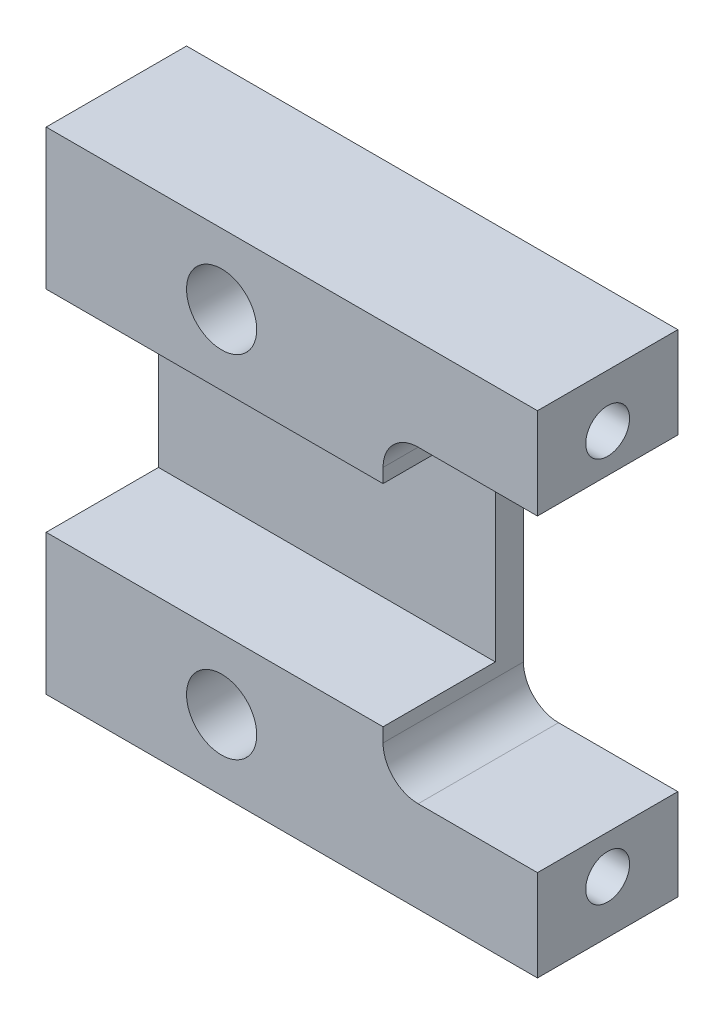
SolidWorks part; units mm, degrees
material "6061-T6 (SS)"
ref_plane "Front Plane" through (0, 0, 0) normal (0, 0, 1) x (1, 0, 0)
ref_plane "Top Plane" through (0, 0, 0) normal (0, 1, 0) x (1, 0, 0)
ref_plane "Right Plane" through (0, 0, 0) normal (1, 0, 0) x (0, 0, -1)
sketch "Sketch1" plane through (0, 0, 0) normal (0, 0, 1) x (1, 0, 0)
  line L1 (-44.45, -44.45) -> (44.45, -44.45)
  line L2 (-44.45, -44.45) -> (-44.45, 44.45)
  line L3 (-44.45, 44.45) -> (44.45, 44.45)
  line L4 (44.45, -44.45) -> (44.45, 44.45)
  line L5 (-44.45, -44.45) -> (44.45, 44.45) construction
  line L6 (-44.45, 44.45) -> (44.45, -44.45) construction
  point P0 (0, 0)
  dimension "D1" = 88.9
  dimension "D2" = 88.9
extrude "Extrude1" add sketch "Sketch1" along normal blind 25.4
sketch "Sketch2" plane through (44.45, 0, 0) normal (1, 0, 0) x (0, 0, -1)
  line L0 (-12.7, 44.45) -> (-12.7, 34.925) construction
  line L1 (-25.4, 44.45) -> (0, 44.45) construction
  dimension "D1" = 9.525
hole_wizard "Tap Drill for 3/8-16 Tap2" positions "Sketch4" profile "Sketch3" hole size "3/8-16" standard "Ansi Inch"
sketch "Sketch4" plane through (44.45, 0, 0) normal (1, 0, 0) x (0, 0, -1)
  point P1 (-12.7, 34.925)
sketch "Sketch3" plane through (44.45, 34.925, 12.7) normal (0, 1, 0) x (0, 0, -1)
  line L0 (0, 0) -> (0, 20.1647)
  line L1 (0, 20.1647) -> (3.9687, 17.78)
  line L2 (3.9687, 17.78) -> (3.9687, 0)
  line L5 (3.9687, 0) -> (0, 0)
  line L10 (0, 20.1647) -> (-3.9688, 17.78) construction
  line L11 (0, -6.35) -> (0, 107.95) construction
  dimension "Hole Dia." = 7.9375
  dimension "Hole Depth" = 17.78
  dimension "Drill Angle" = 118
mirror "Mirror1" about plane through (0, 0, 0) normal (0, 1, 0) of "Tap Drill for 3/8-16 Tap2"
sketch "Sketch5" plane through (0, 0, 25.4) normal (0, 0, 1) x (1, 0, 0)
  line L0 (-12.7, 44.45) -> (-12.7, 31.75) construction
  line L5 (44.45, 44.45) -> (-44.45, 44.45) construction
  line L6 (-44.45, 44.45) -> (-44.45, -44.45) construction
  dimension "D1" = 12.7
  dimension "D2" = 31.75
hole_wizard "1/2 (0.5) Diameter Hole1" positions "Sketch7" profile "Sketch6" hole size "1/2" standard "Ansi Inch" end condition through all
sketch "Sketch7" plane through (0, 0, 25.4) normal (0, 0, 1) x (1, 0, 0)
  point P6 (-12.7, 31.75)
sketch "Sketch6" plane through (-12.7, 31.75, 25.4) normal (1, 0, 0) x (0, -1, 0)
  line L0 (0, 0) -> (0, 25.4)
  line L1 (0, 25.4) -> (6.35, 25.4)
  line L2 (6.35, 25.4) -> (6.35, 0)
  line L5 (6.35, 0) -> (0, 0)
  line L11 (0, -6.35) -> (0, 107.95) construction
  dimension "Thru Hole Dia." = 12.7
  dimension "Thru Hole Depth" = 25.4
mirror "Mirror3" about plane through (0, 0, 0) normal (0, 1, 0) of "1/2 (0.5) Diameter Hole1"
sketch "Sketch15" plane through (0, 0, 25.4) normal (0, 0, 1) x (1, 0, 0)
  line L0 (-44.45, 0) -> (-44.45, 19.05)
  line L1 (-44.45, 44.45) -> (-44.45, -44.45) construction
  line L2 (-44.45, 19.05) -> (16.51, 19.05)
  line L3 (16.51, 19.05) -> (16.51, 27.94)
  line L4 (16.51, 27.94) -> (44.45, 27.94)
  line L5 (44.45, -44.45) -> (44.45, 44.45) construction
  line L6 (44.45, 27.94) -> (44.45, 0)
  line L7 (44.45, 0) -> (-44.45, 0)
  dimension "D1" = 19.05
  dimension "D2" = 27.94
  dimension "D3" = 27.94
extrude "Extrude5" cut sketch "Sketch15" against normal blind 20.32
mirror "Mirror4" about plane through (0, 0, 0) normal (0, 1, 0) of "Extrude5"
sketch "Sketch16" plane through (0, 0, 5.08) normal (0, 0, 1) x (1, 0, 0)
  line L1 (16.51, 27.94) -> (44.45, 27.94)
  line L2 (16.51, 27.94) -> (16.51, -27.94)
  line L3 (16.51, -27.94) -> (44.45, -27.94)
  line L4 (44.45, 27.94) -> (44.45, -27.94)
extrude "Extrude6" cut sketch "Sketch16" against normal through all
fillet "Fillet2" radius 6.35 2 edges at (16.51, -27.94, 12.7) (16.51, 27.94, 12.7)
sketch "Sketch17" plane through (-44.45, 0, 0) normal (-1, 0, 0) x (0, 0, 1)
  line L0 (12.7, 44.45) -> (12.7, 31.75) construction
  line L1 (25.4, 44.45) -> (0, 44.45) construction
  dimension "D1" = 12.7
hole_wizard "Tap Drill for 1/2-13 Tap2" positions "3DSketch1" profile "Sketch18" hole size "1/2-13" standard "Ansi Inch"
sketch3d "3DSketch1"
  point P0 (-44.45, 31.75, 12.7)
sketch "Sketch18" plane through (-44.45, 31.75, 12.7) normal (0, 1, 0) x (0, 0, 1)
  line L0 (0, 0) -> (0, 20.9995)
  line L1 (0, 20.9995) -> (5.3581, 17.78)
  line L2 (5.3581, 17.78) -> (5.3581, 0)
  line L5 (5.3581, 0) -> (0, 0)
  line L10 (0, 20.9995) -> (-5.3581, 17.78) construction
  line L11 (0, -6.35) -> (0, 107.95) construction
  dimension "Hole Dia." = 10.7163
  dimension "Hole Depth" = 17.78
  dimension "Drill Angle" = 118
mirror "Mirror5" about plane through (0, 0, 0) normal (0, 1, 0) of "Tap Drill for 1/2-13 Tap2"
